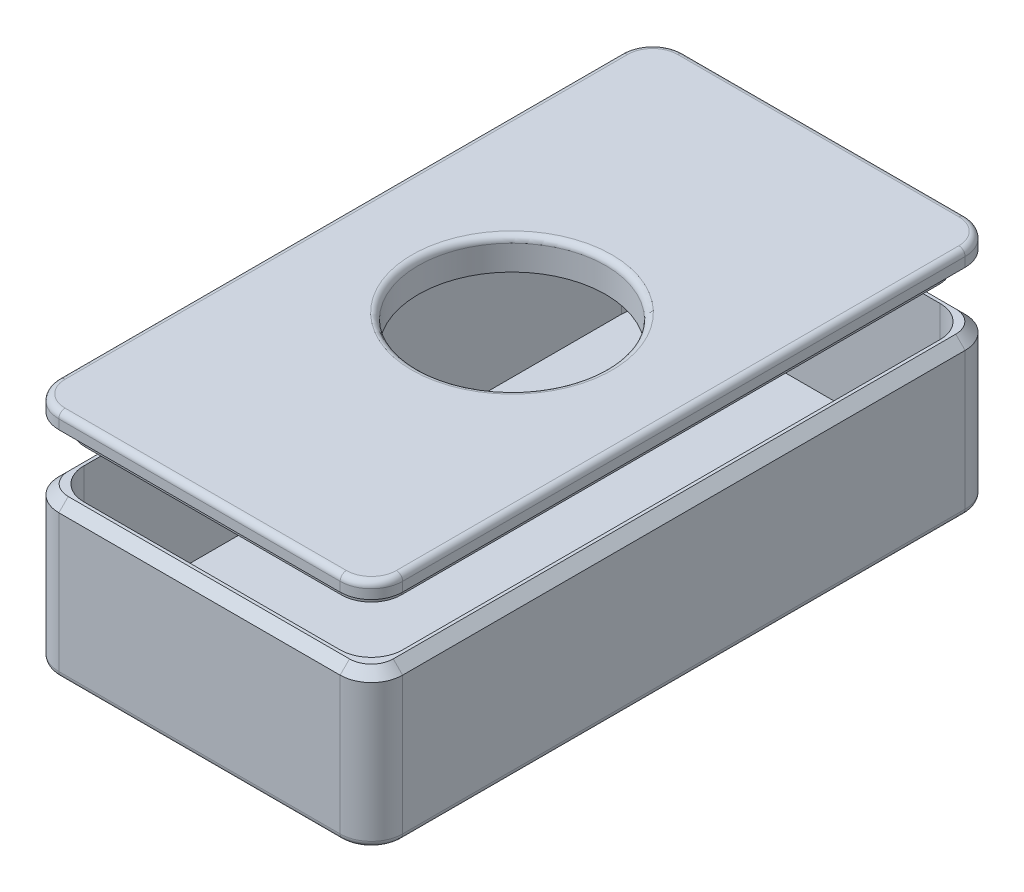
SolidWorks part; units mm, degrees
ref_plane "Front Plane" through (0, 0, 0) normal (0, 0, 1) x (1, 0, 0)
ref_plane "Top Plane" through (0, 0, 0) normal (0, 1, 0) x (1, 0, 0)
ref_plane "Right Plane" through (0, 0, 0) normal (1, 0, 0) x (0, 0, -1)
sketch "Sketch1" plane through (0, 0, 0) normal (0, 1, 0) x (1, 0, 0)
  line L0 (-2, 98) -> (53, 98)
  line L1 (0, 0) -> (51, 0)
  line L2 (0, 0) -> (0, 96)
  line L3 (0, 96) -> (51, 96)
  line L4 (51, 0) -> (51, 96)
  line L5 (53, -2) -> (53, 98)
  line L6 (-2, -2) -> (53, -2)
  line L7 (-2, -2) -> (-2, 98)
  dimension "D1" = 51
  dimension "D2" = 96
  dimension "D3" = 2
extrude "Boss-Extrude1" add sketch "Sketch1" along normal blind 22
sketch "Sketch2" plane through (0, 0, 0) normal (0, -1, 0) x (1, 0, 0)
  line L1 (53, 2) -> (-2, 2)
  line L2 (53, 2) -> (53, -98)
  line L3 (53, -98) -> (-2, -98)
  line L4 (-2, 2) -> (-2, -98)
extrude "Boss-Extrude2" add sketch "Sketch2" along normal blind 2.5
fillet "Fillet1" radius 5 4 edges at (51, 11, -96) (0, 11, -96) (51, 11, 0) (0, 11, 0)
ref_plane "Plane1" through (0, 32, 0) normal (0, 1, 0) x (1, 0, 0)
sketch "Sketch3" plane through (0, 32, 0) normal (0, 1, 0) x (1, 0, 0)
  line L4 (51, 5) -> (51, 91)
  line L5 (46, 96) -> (5, 96)
  line L6 (0, 91) -> (0, 5)
  line L7 (5, 0) -> (46, 0)
  line L8 (51, 5) -> (51, 91)
  line L9 (46, 96) -> (5, 96)
  line L10 (0, 91) -> (0, 5)
  line L11 (5, 0) -> (46, 0)
  line L12 (-2, 98) -> (-2, -2)
  line L13 (-2, -2) -> (53, -2)
  line L14 (53, -2) -> (53, 98)
  line L15 (53, 98) -> (-2, 98)
  line L16 (-2, 98) -> (-2, -2)
  line L17 (-2, -2) -> (53, -2)
  line L18 (53, -2) -> (53, 98)
  line L19 (53, 98) -> (-2, 98)
  arc A4 (51, 91) -> (46, 96) centre (46, 91) ccw
  arc A5 (5, 96) -> (0, 91) centre (5, 91) ccw
  arc A6 (0, 5) -> (5, 0) centre (5, 5) ccw
  arc A7 (46, 0) -> (51, 5) centre (46, 5) ccw
  arc A8 (51, 91) -> (46, 96) centre (46, 91) ccw
  arc A9 (5, 96) -> (0, 91) centre (5, 91) ccw
  arc A10 (0, 5) -> (5, 0) centre (5, 5) ccw
  arc A11 (46, 0) -> (51, 5) centre (46, 5) ccw
  dimension "D1" = 0
  dimension "D2" = 0
extrude "Boss-Extrude3" add sketch "Sketch3" along normal blind 2.5 separate body contours L16 L17 L18 L19
extrude "Boss-Extrude4" add sketch "Sketch3<3>" against normal blind 2.5 draft 5 contours A10 L11 A11 L8 A8 L9 A9 L10
sketch "Sketch3<3>" plane through (0, 32, 0) normal (0, 1, 0) x (1, 0, 0) same geometry as "Sketch3"
fillet "Fillet2" radius 5 4 edges at (-2, 33.25, -98) (53, 33.25, -98) (53, 33.25, 2) (-2, 33.25, 2)
fillet "Fillet3" radius 1 8 edges at (-0.5355, 34.5, 0.5355) (-2, 34.5, -48) (-0.5355, 34.5, -96.5355) (25.5, 34.5, -98) (51.5355, 34.5, -96.5355) (53, 34.5, -48) (51.5355, 34.5, 0.5355) (25.5, 34.5, 2)
fillet "Fillet4" radius 5 4 edges at (53, 9.75, 2) (53, 9.75, -98) (-2, 9.75, -98) (-2, 9.75, 2)
chamfer "Chamfer1" distance 1.5 angle 45 8 edges at (25.5, 22, -98) (-0.5355, 22, -96.5355) (51.5355, 22, -96.5355) (-2, 22, -48) (53, 22, -48) (-0.5355, 22, 0.5355) (51.5355, 22, 0.5355) (25.5, 22, 2)
fillet "Fillet5" radius 1 8 edges at (51.5355, -2.5, 0.5355) (53, -2.5, -48) (51.5355, -2.5, -96.5355) (25.5, -2.5, -98) (-0.5355, -2.5, -96.5355) (-2, -2.5, -48) (-0.5355, -2.5, 0.5355) (25.5, -2.5, 2)
sketch "Sketch4" plane through (0, 34.5, 0) normal (0, 1, 0) x (1, 0, 0)
  circle A0 centre (25.5, 48) radius 15
  dimension "D1" = 30
extrude "Cut-Extrude1" cut sketch "Sketch4" against normal up to next (5 mm away)
fillet "Fillet6" radius 1 1 edges at (25.5, 34.5, -33)
